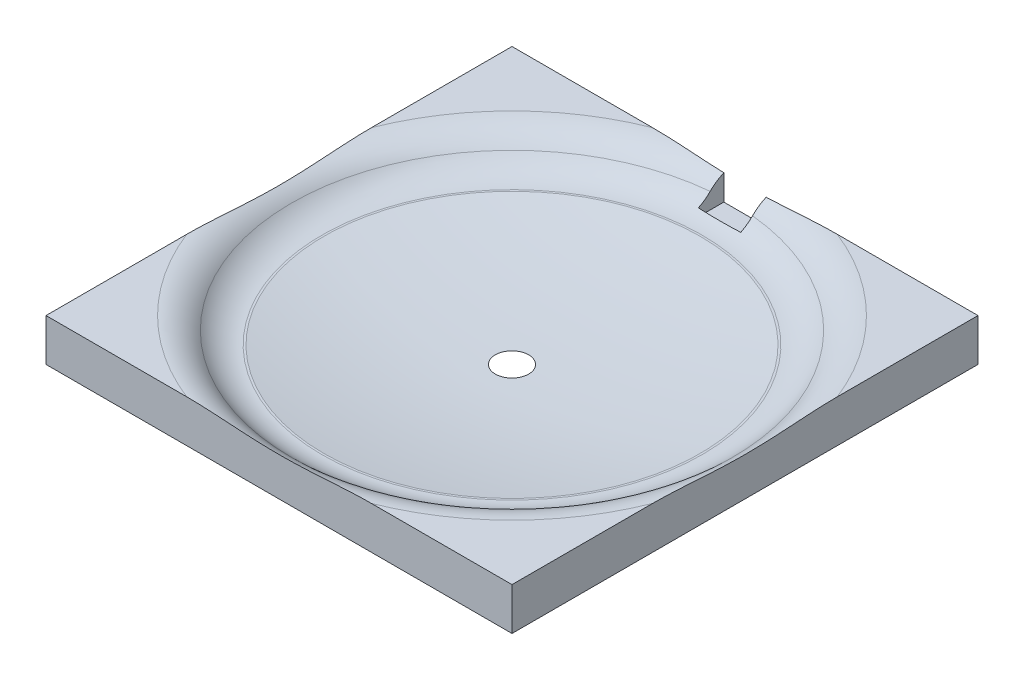
SolidWorks part; units mm, degrees
ref_plane "Front Plane" through (0, 0, 0) normal (0, 0, 1) x (1, 0, 0)
ref_plane "Top Plane" through (0, 0, 0) normal (0, 1, 0) x (1, 0, 0)
ref_plane "Right Plane" through (0, 0, 0) normal (1, 0, 0) x (0, 0, -1)
sketch "Sketch1" plane through (0, 0, 0) normal (0, 1, 0) x (1, 0, 0)
  line L1 (55, 55) -> (-55, 55)
  line L2 (55, 55) -> (55, -55)
  line L3 (55, -55) -> (-55, -55)
  line L4 (-55, 55) -> (-55, -55)
  line L5 (55, 55) -> (-55, -55) construction
  line L6 (55, -55) -> (-55, 55) construction
  point P0 (0, 0)
  dimension "D1" = 110
  dimension "D2" = 110
extrude "Boss-Extrude1" add sketch "Sketch1" along normal blind 10
sketch "Sketch2" plane through (0, 10, 0) normal (0, 1, 0) x (1, 0, 0)
  circle A0 centre (0, 0) radius 50
  dimension "D1" = 100
extrude "Cut-Extrude1" cut sketch "Sketch2" against normal blind 6
fillet "Fillet1" radius 10 1 edges at (0, 10, 50)
fillet "Fillet2" radius 10 1 edges at (0, 4, 50)
sketch "Sketch3" plane through (0, 0, 0) normal (1, 0, 0) x (0, 0, -1)
  line L0 (0, 0) -> (0, 10.2858)
  line L1 (0, 10.2858) -> (-44.6394, 4.0438)
  spline S0 degree 2 poles (0, 0) (-22.4295, -0.1944) (-44.6394, 4.0438) knots 0 0 0 1 1 1
  point P4 (-3.934, 0)
revolve "Cut-Revolve3" cut sketch "Sketch3" angle 360 about L0
sketch "Sketch4" plane through (0, 0, -55) normal (0, 0, -1) x (-1, 0, 0)
  line L0 (0, 6.2394) -> (0, -6.2394) construction
  line L1 (-5, 9.1918) -> (5, 9.1918)
  line L2 (-5, 9.1918) -> (-5, 3.1918)
  line L3 (-5, 3.1918) -> (5, 3.1918)
  line L4 (5, 9.1918) -> (5, 3.1918)
  spline S0 degree 3 poles (21.8063, 10) (19.9848, 10) (18.1663, 9.9331) (14.5318, 9.7451) (12.7157, 9.6237) (9.083, 9.3939) (7.2664, 9.2857) (3.6302, 9.134) (1.8095, 9.0911) (-1.829, 9.0914) (-3.6466, 9.1346) (-7.2794, 9.2864) (-9.0945, 9.3946) (-12.7243, 9.6243) (-14.539, 9.7455) (-18.1703, 9.9333) (-19.9871, 10) (-21.8063, 10) knots 0 0 0 0 0.125 0.125 0.25 0.25 0.375 0.375 0.5 0.5 0.625 0.625 0.75 0.75 0.875 0.875 1 1 1 1 construction
  dimension "D1" = 6
  dimension "D2" = 10
  dimension "D3" = 5
extrude "Cut-Extrude2" cut sketch "Sketch4" against normal blind 6
